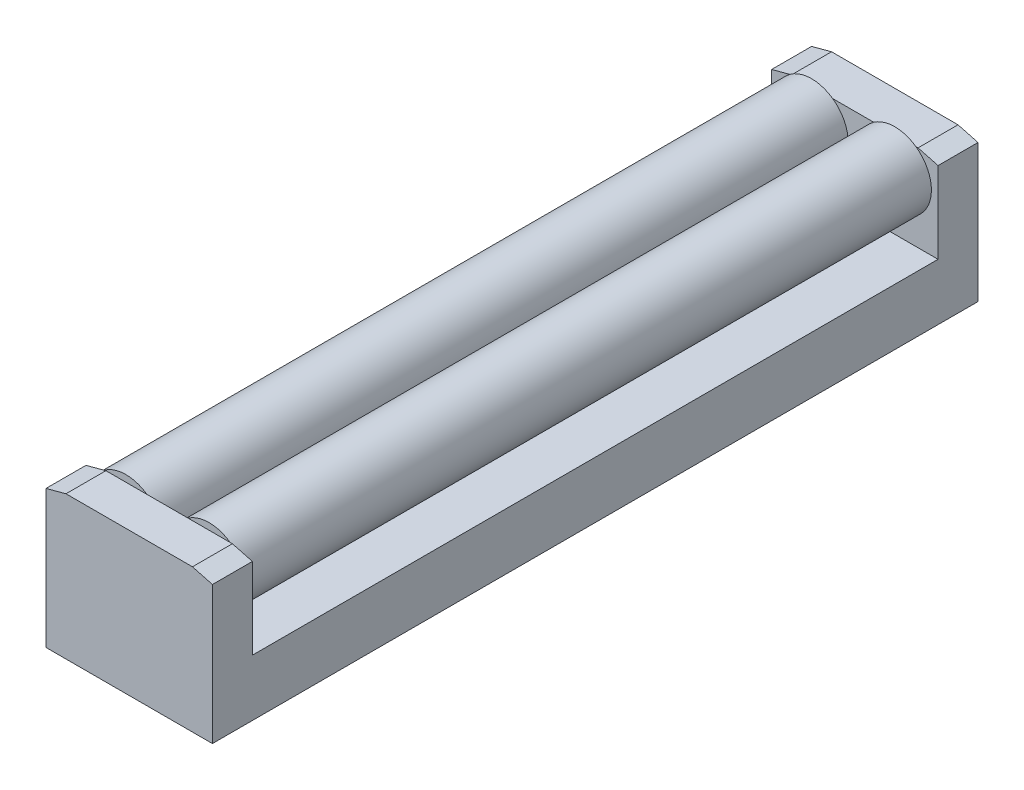
SolidWorks part; units mm, degrees
ref_plane "Frontale" through (0, 0, 0) normal (0, 0, 1) x (1, 0, 0)
ref_plane "Superiore" through (0, 0, 0) normal (0, 1, 0) x (1, 0, 0)
ref_plane "Destro" through (0, 0, 0) normal (1, 0, 0) x (0, 0, -1)
sketch "Schizzo1" plane through (0, 0, 0) normal (0, 0, 1) x (1, 0, 0)
  line L1 (0, 0) -> (25, 0)
  line L2 (0, 0) -> (0, 21.5)
  line L3 (0, 21.5) -> (25, 21.5)
  line L4 (25, 0) -> (25, 21.5)
  dimension "D1" = 25
  dimension "D2" = 21.5
extrude "Estrusione1" add sketch "Schizzo1" along normal blind 115
sketch "Schizzo6" plane through (25, 0, 0) normal (1, 0, 0) x (0, 0, -1)
  line L1 (-115, 0) -> (-115, 21.5) construction
  line L2 (-115, 0) -> (0, 0) construction
  line L9 (-109, 32.1395) -> (-6, 32.1395)
  line L10 (-109, 32.1395) -> (-109, 8.5)
  line L11 (-109, 8.5) -> (-6, 8.5)
  line L12 (-6, 32.1395) -> (-6, 8.5)
  line L13 (-317.5773, 8.5) -> (13.8875, 8.5) construction
  dimension "D1" = 6
  dimension "D2" = 8.5
  dimension "D5" = 6
extrude "Taglio-Estrusione4" cut sketch "Schizzo6" against normal blind 84
sketch "Schizzo7" plane through (0, 0, 6) normal (0, 0, 1) x (1, 0, 0)
  line L0 (-0.9369, 17) -> (39.6559, 17) construction
  line L1 (0, 21.5) -> (0, 0) construction
  line L4 (0, 0) -> (25, 0) construction
  circle A0 centre (6, 17) radius 5.5
  circle A1 centre (18.5, 17) radius 5.5
  dimension "D1" = 11
  dimension "D2" = 11
  dimension "D3" = 17
  dimension "D4" = 12.5
  dimension "D6" = 6
extrude "Estrusione4" add sketch "Schizzo7" along normal up to surface (103 mm away) up to face at (12.5, 15, 109)
chamfer "Smusso1" distance 3 angle 15 4 edges at (0, 21.5, 3) (25, 21.5, 3) (25, 21.5, 112) (0, 21.5, 112) first distance on face at (12.375, 21.5, 4.5) first distance on face at (12.375, 21.5, 110.5)
sketch "Schizzo8" plane through (0, 0, 0) normal (0, -1, 0) x (1, 0, 0)
  line L0 (12, 120.9167) -> (12, -3.7523) construction
  line L1 (25, 115) -> (25, 0) construction
  line L2 (0, 115) -> (25, 115) construction
  circle A0 centre (12, 105.5) radius 3
  circle A1 centre (12, 9.5) radius 3
  dimension "D1" = 6
  dimension "D2" = 6
  dimension "D3" = 96
  dimension "D4" = 13
  dimension "D5" = 9.5
extrude "Taglio-Estrusione5" cut sketch "Schizzo8" against normal up to surface (8.5 mm away) up to face at (12.5, 8.5, 57.5)
